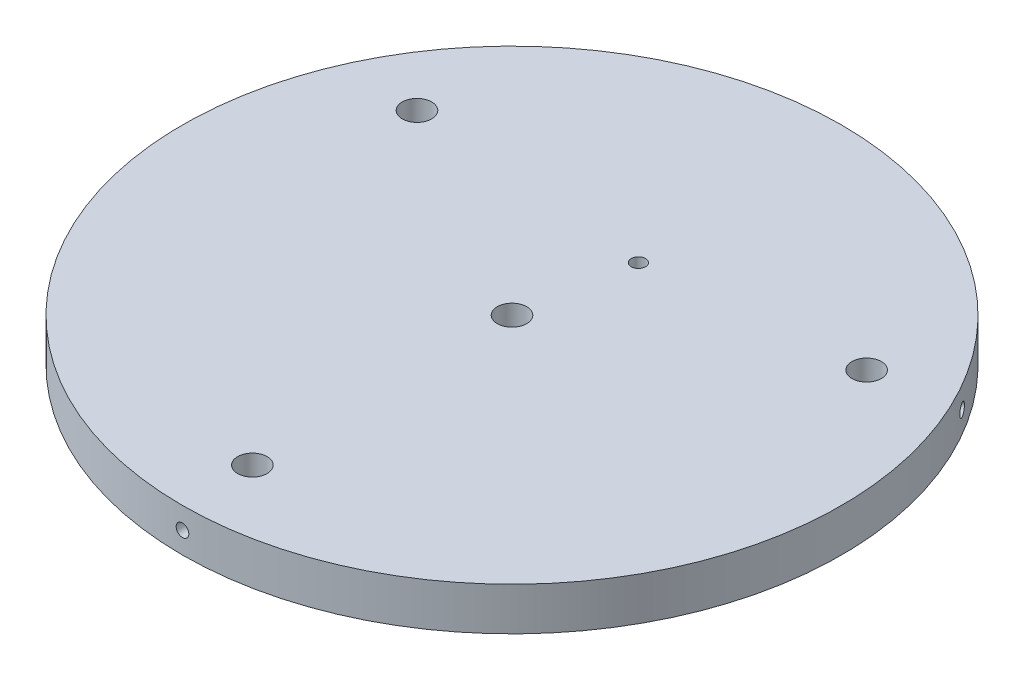
SolidWorks part; units mm, degrees
material "6061-T4 (SS)"
ref_plane "Front Plane" through (0, 0, 0) normal (0, 0, 1) x (1, 0, 0)
ref_plane "Top Plane" through (0, 0, 0) normal (0, 1, 0) x (1, 0, 0)
ref_plane "Right Plane" through (0, 0, 0) normal (1, 0, 0) x (0, 0, -1)
sketch "Sketch1" plane through (0, 0, 0) normal (0, 1, 0) x (1, 0, 0)
  line L0 (0, 0) -> (-63.2415, 36.5125) construction
  line L1 (0, 0) -> (0, -73.025) construction
  line L2 (0, 0) -> (63.2415, 36.5125) construction
  line L3 (0, 0) -> (7.2777, 23.8043) construction
  circle A0 centre (0, 0) radius 73.025
  circle A1 centre (-49.8233, 28.7655) radius 3.2639
  circle A2 centre (49.8233, 28.7655) radius 3.2639
  circle A3 centre (0, -57.531) radius 3.2639
  circle A4 centre (0, 0) radius 3.2639
  circle A5 centre (7.2777, 23.8043) radius 1.5875 construction
  point P15 (0, 0)
  dimension "D1" = 146.05
  dimension "D4" = 6.5278
  dimension "D7" = 6.5278
  dimension "D8" = 3.175
  dimension "D2" = 120
  dimension "D3" = 120
  dimension "D5" = 57.531
  dimension "D9" = 24.892
  dimension "D10" = 163
  dimension "D6" = 3
extrude "Boss-Extrude1" add sketch "Sketch1" along normal blind 9.525
ref_plane "Plane1" through (0, 0, 73.025) normal (0, 0, 1) x (1, 0, 0)
sketch "Sketch3" plane through (0, 0, 0) normal (0, 0, 1) x (1, 0, 0)
  line L0 (0, 0) -> (0, 9.525) construction
  line L1 (73.025, 9.525) -> (-73.025, 9.525) construction
sketch "Sketch4" plane through (0, 0, 73.025) normal (0, 0, 1) x (1, 0, 0)
  line L0 (0, 0) -> (0, 9.525) construction
  circle A0 centre (0, 4.7625) radius 1.397
  dimension "D1" = 2.794
extrude "Cut-Extrude1" cut sketch "Sketch4" against normal blind 6.35
pattern_circular "CirPattern1" count 3 over 360 about axis through (0, 0, 0) along (0, 1, 0) of "Cut-Extrude1" reverse direction yes
sketch "Sketch5" plane through (0, 9.525, 0) normal (0, 1, 0) x (1, 0, 0)
  circle A0 centre (3.9182, 24.0893) radius 1.5875
  point P0 (3.9182, 24.0893)
  dimension "D1" = 3.175
extrude "Cut-Extrude2" cut sketch "Sketch5" against normal through all both
